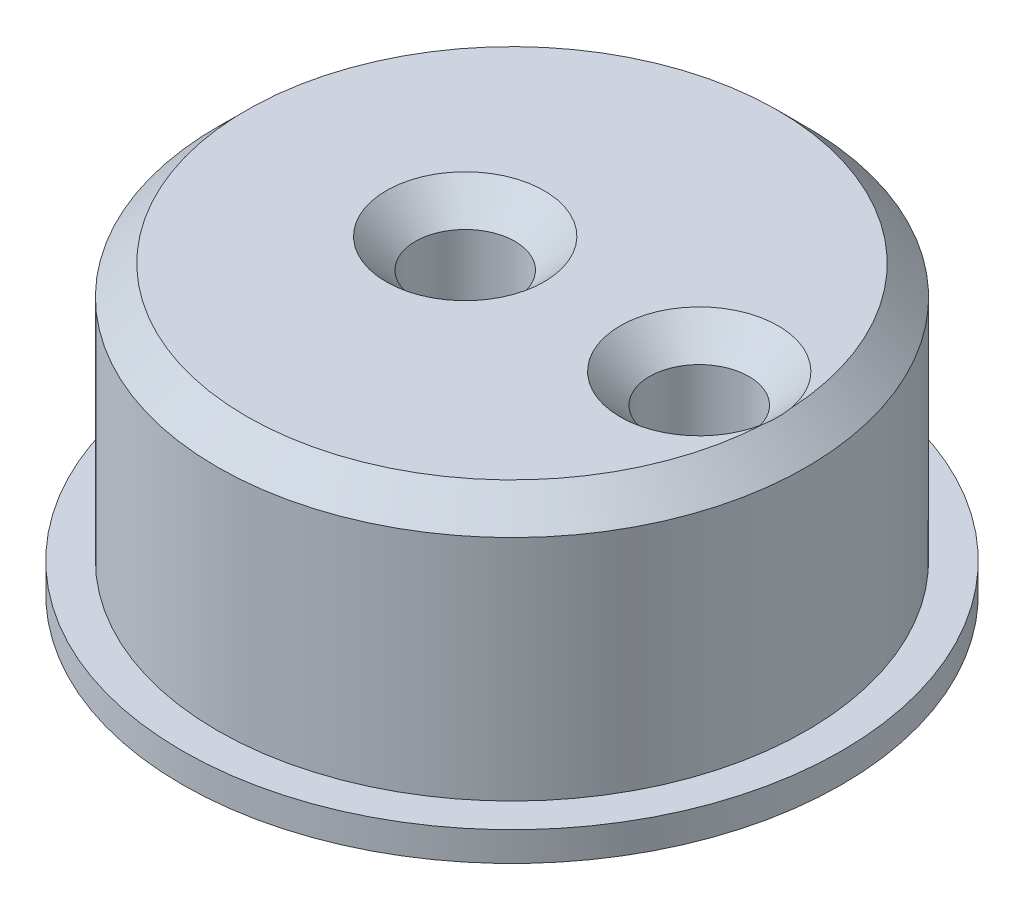
SolidWorks part; units mm, degrees
ref_plane "前视基准面" through (0, 0, 0) normal (0, 0, 1) x (1, 0, 0)
ref_plane "上视基准面" through (0, 0, 0) normal (0, 1, 0) x (1, 0, 0)
ref_plane "右视基准面" through (0, 0, 0) normal (1, 0, 0) x (0, 0, -1)
other "Configuration Table"
sketch "草图1" plane through (0, 0, 0) normal (0, 1, 0) x (1, 0, 0)
  line L0 (1.2, 6.4178) -> (1.2, -6.4114) construction
  line L1 (-5.7349, 0) -> (5.8104, 0) construction
  circle A0 centre (0, 0) radius 5.035
  circle A1 centre (3.2, 0) radius 0.85
  circle A2 centre (-0.8, 0) radius 0.85
  dimension "D1" = 10.07
  dimension "D3" = 4
  dimension "D4" = 1.7
  dimension "D2" = 1.2
extrude "凸台-拉伸1" add sketch "草图1" along normal blind 4.4
sketch "草图3" plane through (0, 0, 0) normal (0, -1, 0) x (1, 0, 0)
  circle A0 centre (3.2, 0) radius 0.85 construction
  circle A1 centre (0, 0) radius 5.035 construction
  circle A3 centre (-0.8, 0) radius 0.85 construction
  circle A4 centre (3.2, 0) radius 0.85
  circle A5 centre (-0.8, 0) radius 0.85
  circle A6 centre (0, 0) radius 5.035 construction
  circle A7 centre (0, 0) radius 5.635
  dimension "D1" = 0.6
extrude "凸台-拉伸2" add sketch "草图3" along normal blind 0.5
chamfer "倒角1" distance 0.5 angle 45 5 edges at (0, 4.4, 5.035) (-0.8, 4.4, -0.85) (3.2, 4.4, 0.85) (-0.8, -0.5, -0.85) (3.2, -0.5, -0.85)
ref_axis "基准轴1" through (0, 3.9, 0) along (0, -1, 0)
sketch "草图2" plane through (0, 0, 0) normal (0, 1, 0) x (1, 0, 0)
  line L0 (-5.9042, 0) -> (6.2358, 0) construction
